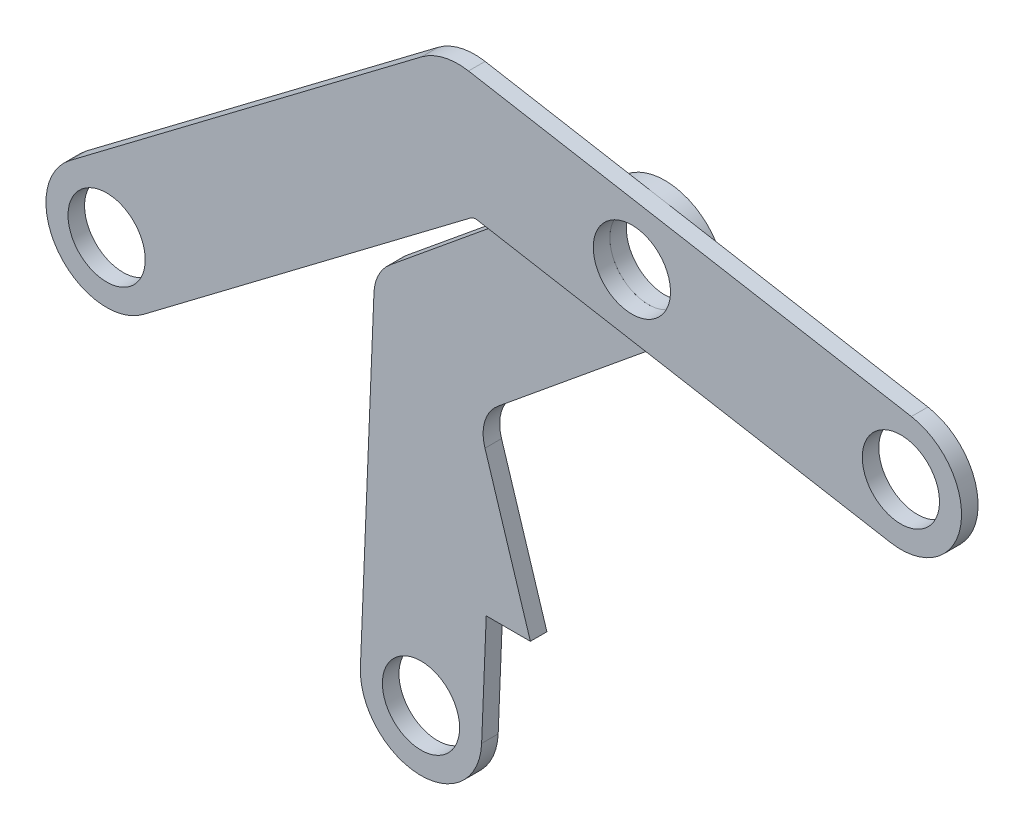
SolidWorks part; units mm, degrees
ref_plane "Front Plane" through (0, 0, 0) normal (0, 0, 1) x (1, 0, 0)
ref_plane "Top Plane" through (0, 0, 0) normal (0, 1, 0) x (1, 0, 0)
ref_plane "Right Plane" through (0, 0, 0) normal (1, 0, 0) x (0, 0, -1)
sketch "Sketch1" plane through (0, 0, 0) normal (0, 0, 1) x (1, 0, 0)
  line L0 (0, -34.925) -> (190.5, -34.925) construction
  line L1 (-190.5, -12.7) -> (190.5, -12.7) construction
  line L2 (-190.5, -12.7) -> (-190.5, 12.7) construction
  line L3 (-190.5, 12.7) -> (190.5, 12.7) construction
  line L4 (190.5, -12.7) -> (190.5, 12.7) construction
  line L5 (-190.5, -12.7) -> (190.5, 12.7) construction
  line L6 (-190.5, 12.7) -> (190.5, -12.7) construction
  line L7 (190.5, 12.7) -> (304.8, 155.575) construction
  line L8 (-190.5, -203.2) -> (190.5, -203.2) construction
  line L9 (8.2376, 104.775) -> (84.4376, 104.775)
  line L10 (8.2376, 104.775) -> (8.2376, 79.375)
  line L11 (8.2376, 79.375) -> (84.4376, 79.375)
  line L12 (84.4376, 104.775) -> (84.4376, 79.375)
  line L13 (190.5, -482.6) -> (-190.5, -482.6) construction
  line L14 (190.5, -482.6) -> (190.5, -139.7) construction
  line L15 (190.5, -139.7) -> (-190.5, -139.7) construction
  line L16 (-190.5, -482.6) -> (-190.5, -139.7) construction
  line L17 (190.5, -482.6) -> (-190.5, -139.7) construction
  line L18 (190.5, -139.7) -> (-190.5, -482.6) construction
  line L19 (190.5, -419.1) -> (-190.5, -419.1) construction
  circle A0 centre (0, 6.35) radius 41.275 construction
  circle A1 centre (263.2484, 44.45) radius 79.375 construction
  circle A2 centre (366.2836, 44.45) radius 79.375 construction
  circle A3 centre (304.8, 155.575) radius 47.625
  circle A4 centre (240.0852, 74.6815) radius 79.375 construction
  circle A7 centre (0, 92.075) radius 79.375 construction
  circle A8 centre (92.6752, -311.15) radius 79.375 construction
  circle A9 centre (0, -311.15) radius 79.375 construction
  circle A10 centre (46.3376, -203.2) radius 38.1
  circle A11 centre (46.3376, -419.1) radius 38.1
  circle A14 centre (143.882, 177.9841) radius 20.6375
  circle A15 centre (194.8848, 91.9538) radius 79.375 construction
  circle A16 centre (92.6752, 92.075) radius 79.375 construction
  point P0 (0, 0)
  point P26 (84.4376, 92.075)
  point P32 (0, -311.15)
  point P47 (46.3376, 79.375)
  dimension "D3" = 82.55
  dimension "D5" = 158.75
  dimension "D6" = 95.25
  dimension "D9" = 41.275
  dimension "D17" = 76.2
  dimension "D1" = 381
  dimension "D2" = 25.4
  dimension "D4" = 6.35
  dimension "D7" = 114.3
  dimension "D8" = 190.5
  dimension "D10" = 76.2
  dimension "D11" = 25.4
  dimension "D12" = 381
  dimension "D13" = 342.9
  dimension "D14" = 127
  dimension "D15" = 63.5
  dimension "D16" = 63.5
  dimension "D18" = 381
sketch "Sketch4" plane through (0, 0, 0) normal (0, 0, 1) x (1, 0, 0)
  line L0 (-190.5, 12.7) -> (190.5, 12.7) construction
  line L1 (0, -34.925) -> (190.5, -34.925) construction
  line L2 (-190.5, -12.7) -> (-190.5, 12.7) construction
  line L3 (-190.5, -12.7) -> (190.5, -12.7) construction
  line L4 (190.5, -12.7) -> (190.5, 12.7) construction
  line L5 (-190.5, 12.7) -> (190.5, 12.7) construction
  line L6 (0, -34.925) -> (190.5, -34.925) construction
  line L7 (-190.5, -12.7) -> (-190.5, 12.7) construction
  line L8 (-190.5, -12.7) -> (190.5, -12.7) construction
  line L9 (190.5, -12.7) -> (190.5, 12.7) construction
  line L10 (102.5799, 225.5717) -> (117.1514, 176.9064)
  line L11 (177.3452, 177.9841) -> (76.2, 101.6)
  line L12 (227.3778, 169.1874) -> (161.925, 25.4)
  line L13 (76.2, 101.6) -> (102.5799, 225.5717)
  line L14 (117.1514, 176.9064) -> (139.7, 101.6)
  line L15 (117.1514, 176.9064) -> (161.925, 25.4)
  line L16 (177.3452, 177.9841) -> (227.3778, 169.1874)
  line L17 (227.3778, 169.1874) -> (304.8, 155.575)
  line L18 (-76.2, 101.6) -> (-177.3452, 177.9841)
  line L19 (-102.5799, 225.5717) -> (-117.1514, 176.9064)
  line L20 (-227.3778, 169.1874) -> (-161.925, 25.4)
  line L21 (-76.2, 101.6) -> (-102.5799, 225.5717)
  line L22 (-177.3452, 177.9841) -> (-227.3778, 169.1874)
  line L23 (-117.1514, 176.9064) -> (-161.925, 25.4)
  line L24 (-227.3778, 169.1874) -> (-304.8, 155.575)
  line L25 (-117.1514, 176.9064) -> (-139.7, 101.6)
  circle A0 centre (143.882, 177.9841) radius 20.6375 construction
  circle A1 centre (304.8, 155.575) radius 47.625 construction
  circle A2 centre (143.882, 177.9841) radius 20.6375 construction
  circle A3 centre (304.8, 155.575) radius 47.625 construction
  circle A4 centre (139.7, 101.6) radius 47.625 construction
  dimension "D7" = 28.575
  dimension "D1" = 50.8
  dimension "D2" = 50.8
  dimension "D3" = 12.7
  dimension "D4" = 28.575
  dimension "D5" = 63.5
  dimension "D6" = 88.9
sketch "Sketch5" plane through (0, 0, 0) normal (0, 0, 1) x (1, 0, 0)
  line L0 (177.3452, 177.9841) -> (76.2, 101.6) construction
  line L1 (177.3452, 177.9841) -> (227.3778, 169.1874) construction
  line L2 (227.3778, 169.1874) -> (304.8, 155.575) construction
  line L3 (227.3778, 169.1874) -> (161.925, 25.4) construction
  line L4 (-76.2, 101.6) -> (-102.5799, 225.5717) construction
  line L5 (-102.5799, 225.5717) -> (-117.1514, 176.9064) construction
  line L6 (-117.1514, 176.9064) -> (-161.925, 25.4) construction
  line L7 (-117.1514, 176.9064) -> (-139.7, 101.6) construction
  line L8 (177.3452, 177.9841) -> (76.2, 101.6) construction
  line L9 (177.3452, 177.9841) -> (227.3778, 169.1874) construction
  line L10 (227.3778, 169.1874) -> (304.8, 155.575) construction
  line L11 (227.3778, 169.1874) -> (161.925, 25.4) construction
  line L12 (-76.2, 101.6) -> (-102.5799, 225.5717) construction
  line L13 (-102.5799, 225.5717) -> (-117.1514, 176.9064) construction
  line L14 (-117.1514, 176.9064) -> (-161.925, 25.4) construction
  line L15 (-117.1514, 176.9064) -> (-139.7, 101.6) construction
  line L16 (174.3213, 160.7854) -> (301.7761, 138.3763)
  line L17 (180.3691, 195.1828) -> (307.8239, 172.7737)
  line L18 (-122.9713, 96.591) -> (-85.8512, 220.5627)
  line L19 (-156.4287, 106.609) -> (-119.3085, 230.5807)
  line L20 (-134.3638, 173.9616) -> (-122.4876, 104.5448)
  line L21 (180.3361, 98.7659) -> (193.4023, 57.15)
  line L22 (-148.2765, 14.507) -> (-88.7294, 89.1167)
  line L23 (-99.939, 179.8512) -> (-86.1374, 99.1806)
  line L24 (144.4771, 26.1145) -> (148.383, 121.4939)
  line L25 (216.305, 182.6904) -> (153.0194, 130.7946)
  line L26 (179.3729, 24.6855) -> (180.7023, 57.15)
  line L27 (238.4506, 155.6843) -> (183.9936, 111.0282)
  line L28 (-119.6599, 221.9372) -> (-93.2801, 97.9655)
  line L29 (-59.1199, 105.2345) -> (-85.4998, 229.2062)
  line L30 (65.6763, 115.5352) -> (166.8215, 191.9193)
  line L31 (86.7237, 87.6648) -> (187.869, 164.0489)
  line L32 (180.7023, 57.15) -> (193.4023, 57.15)
  line L33 (-179.1, 28.5554) -> (-173.2289, 60.5123)
  line L34 (-173.2289, 60.5123) -> (-176.7552, 72.7129)
  line L35 (-176.7552, 72.7129) -> (-134.8514, 84.8241)
  circle A0 centre (-161.925, 25.4) radius 17.4625
  circle A1 centre (-139.7, 101.6) radius 17.4625
  circle A2 centre (-117.1514, 176.9064) radius 17.4625
  circle A3 centre (-102.5799, 225.5717) radius 17.4625
  circle A4 centre (-76.2, 101.6) radius 17.4625
  circle A5 centre (76.2, 101.6) radius 17.4625
  circle A6 centre (177.3452, 177.9841) radius 17.4625
  circle A7 centre (227.3778, 169.1874) radius 17.4625
  circle A8 centre (161.925, 25.4) radius 17.4625
  circle A9 centre (304.8, 155.575) radius 17.4625
  arc A10 (-86.1374, 99.1806) -> (-88.7294, 89.1167) centre (-98.6555, 97.0389) cw
  arc A11 (148.383, 121.4939) -> (153.0194, 130.7946) centre (161.0724, 120.9743) cw
  arc A12 (180.3361, 98.7659) -> (183.9936, 111.0282) centre (191.2412, 102.1899) cw
  dimension "D1" = 34.925
  dimension "D2" = 12.7
  dimension "D5" = 11.43
  dimension "D3" = 47.625
  dimension "D4" = 12.7
  dimension "D6" = 31.75
sketch "Sketch6" plane through (0, 0, 0) normal (0, 0, 1) x (1, 0, 0)
  circle A0 centre (76.2, 101.6) radius 11.1125
  circle A1 centre (76.2, 101.6) radius 14.6685 construction
  circle A3 centre (227.3778, 169.1874) radius 11.1125
  circle A4 centre (304.8, 155.575) radius 11.1125
  circle A5 centre (161.925, 25.4) radius 11.1125
  dimension "D1" = 22.225
  dimension "D2" = 3.556
sketch "Sketch7" plane through (0, 0, 0) normal (0, 0, 1) x (1, 0, 0)
  line L0 (180.3691, 195.1828) -> (307.8239, 172.7737) construction
  line L1 (174.3213, 160.7854) -> (301.7761, 138.3763) construction
  line L2 (86.7237, 87.6648) -> (187.869, 164.0489) construction
  line L3 (65.6763, 115.5352) -> (166.8215, 191.9193) construction
  line L4 (180.3691, 195.1828) -> (307.8239, 172.7737)
  line L5 (182.8938, 159.2782) -> (301.7761, 138.3763)
  line L6 (86.7237, 87.6648) -> (180.9232, 158.8035)
  line L7 (65.6763, 115.5352) -> (166.8215, 191.9193)
  circle A0 centre (227.3778, 169.1874) radius 11.1125 construction
  circle A1 centre (304.8, 155.575) radius 17.4625 construction
  circle A2 centre (304.8, 155.575) radius 11.1125 construction
  circle A3 centre (177.3452, 177.9841) radius 17.4625 construction
  circle A4 centre (76.2, 101.6) radius 11.1125 construction
  circle A5 centre (76.2, 101.6) radius 17.4625 construction
  circle A6 centre (227.3778, 169.1874) radius 11.1125
  arc A7 (301.7761, 138.3763) -> (307.8239, 172.7737) centre (304.8, 155.575) ccw
  circle A8 centre (304.8, 155.575) radius 11.1125
  arc A9 (180.3691, 195.1828) -> (166.8215, 191.9193) centre (177.3452, 177.9841) ccw
  circle A10 centre (76.2, 101.6) radius 11.1125
  arc A11 (65.6763, 115.5352) -> (86.7237, 87.6648) centre (76.2, 101.6) ccw
  arc A12 (182.8938, 159.2782) -> (180.9232, 158.8035) centre (182.4539, 156.7765) ccw
  point P26 (181.8052, 159.4696)
  dimension "D1" = 2.54
sketch "Sketch8" plane through (0, 0, 0) normal (0, 0, 1) x (1, 0, 0)
  line L0 (179.3729, 24.6855) -> (180.7023, 57.15) construction
  line L1 (180.7023, 57.15) -> (193.4023, 57.15) construction
  line L2 (180.3361, 98.7659) -> (193.4023, 57.15) construction
  line L3 (144.4771, 26.1145) -> (148.383, 121.4939) construction
  line L4 (238.4506, 155.6843) -> (183.9936, 111.0282) construction
  line L5 (216.305, 182.6904) -> (153.0194, 130.7946) construction
  line L6 (179.3729, 24.6855) -> (180.7023, 57.15)
  line L7 (180.7023, 57.15) -> (193.4023, 57.15)
  line L8 (180.3361, 98.7659) -> (193.4023, 57.15)
  line L9 (144.4771, 26.1145) -> (148.383, 121.4939)
  line L10 (238.4506, 155.6843) -> (183.9936, 111.0282)
  line L11 (216.305, 182.6904) -> (153.0194, 130.7946)
  circle A0 centre (161.925, 25.4) radius 11.1125 construction
  circle A1 centre (161.925, 25.4) radius 17.4625 construction
  arc A2 (183.9936, 111.0282) -> (180.3361, 98.7659) centre (191.2412, 102.1899) ccw construction
  arc A3 (153.0194, 130.7946) -> (148.383, 121.4939) centre (161.0724, 120.9743) ccw construction
  circle A4 centre (227.3778, 169.1874) radius 11.1125 construction
  circle A5 centre (227.3778, 169.1874) radius 17.4625 construction
  circle A6 centre (161.925, 25.4) radius 11.1125
  arc A7 (144.4771, 26.1145) -> (179.3729, 24.6855) centre (161.925, 25.4) ccw
  arc A8 (183.9936, 111.0282) -> (180.3361, 98.7659) centre (191.2412, 102.1899) ccw
  arc A9 (153.0194, 130.7946) -> (148.383, 121.4939) centre (161.0724, 120.9743) ccw
  circle A10 centre (227.3778, 169.1874) radius 11.1125
  arc A11 (238.4506, 155.6843) -> (216.305, 182.6904) centre (227.3778, 169.1874) ccw
extrude "Boss-Extrude1" add sketch "Sketch7" along normal blind 4.7625
extrude "Boss-Extrude2" add sketch "Sketch8" against normal blind 4.7625 separate body
